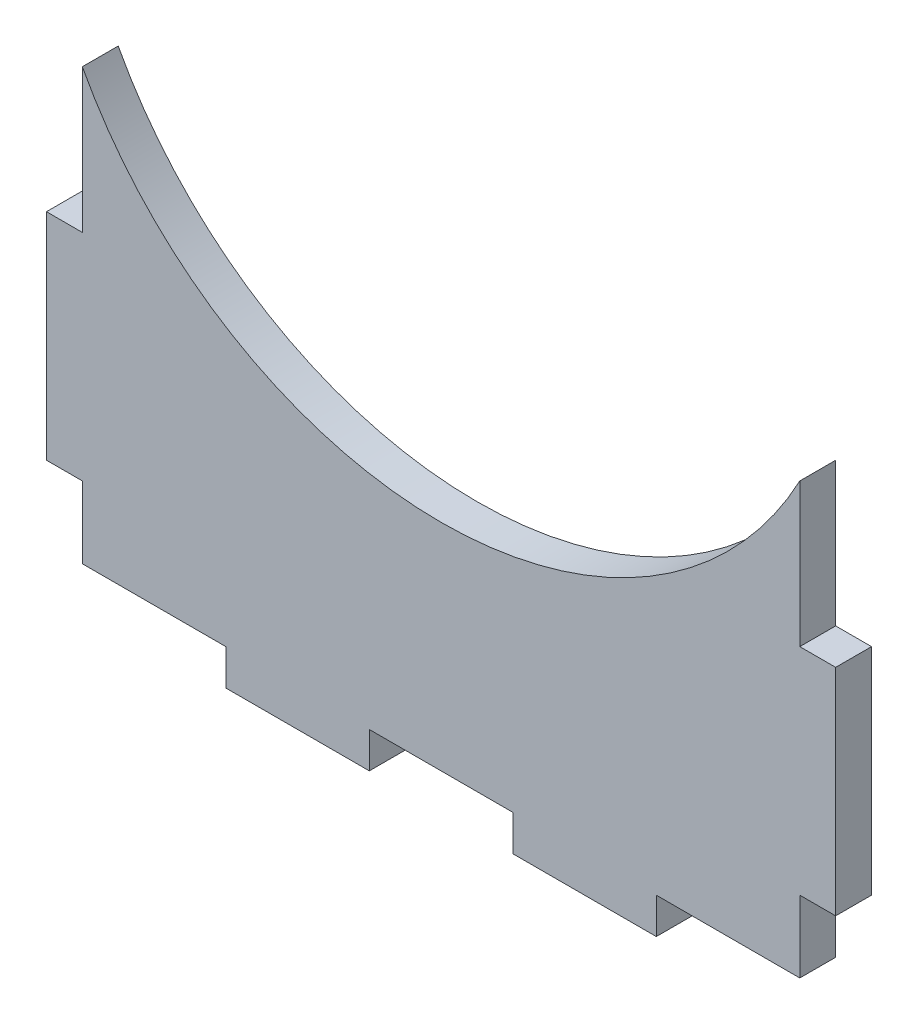
SolidWorks part; units mm, degrees
material "Pine"
ref_plane "Front Plane" through (0, 0, 0) normal (0, 0, 1) x (1, 0, 0)
ref_plane "Top Plane" through (0, 0, 0) normal (0, 1, 0) x (1, 0, 0)
ref_plane "Right Plane" through (0, 0, 0) normal (1, 0, 0) x (0, 0, -1)
sketch "Sketch1" plane through (0, 0, 0) normal (0, 0, 1) x (1, 0, 0)
  line L0 (0, 0) -> (0, 116.4167) construction
  line L3 (63.5, 6.35) -> (63.5, 19.05)
  line L4 (-63.5, 6.35) -> (-63.5, 19.05)
  line L5 (-63.5, 6.35) -> (-38.1, 6.35)
  line L6 (-12.7, 6.35) -> (12.7, 6.35)
  line L8 (-38.1, 6.35) -> (-38.1, 0)
  line L9 (-38.1, 0) -> (-12.7, 0)
  line L10 (-12.7, 6.35) -> (-12.7, 0)
  line L12 (38.1, 6.35) -> (38.1, 0)
  line L13 (38.1, 0) -> (12.7, 0)
  line L14 (12.7, 6.35) -> (12.7, 0)
  line L15 (38.1, 6.35) -> (63.5, 6.35)
  line L17 (-63.5, 57.15) -> (-69.85, 57.15)
  line L19 (-63.5, 19.05) -> (-69.85, 19.05)
  line L20 (-69.85, 57.15) -> (-69.85, 19.05)
  line L21 (-31.7103, 6.35) -> (-107.95, 6.35) construction
  line L22 (-63.5, 57.15) -> (-63.5, 82.55)
  line L23 (63.5, 19.05) -> (69.85, 19.05)
  line L24 (69.85, 57.15) -> (69.85, 19.05)
  line L25 (63.5, 57.15) -> (69.85, 57.15)
  line L26 (63.5, 57.15) -> (63.5, 82.55)
  line L28 (63.5, 6.35) -> (63.5, 0) construction
  arc A0 (-63.5, 82.55) -> (63.5, 82.55) centre (0, 116.4167) ccw
  point P5 (50.4205, 44.45)
  point P26 (0, 44.45)
  point P33 (0, 44.45)
  dimension "D1" = 38.1
  dimension "D2" = 76.2
  dimension "D3" = 38.1
  dimension "D4" = 12.7
  dimension "D5" = 6.35
extrude "Boss-Extrude1" add sketch "Sketch1" along normal up to surface (6.35 mm away)
